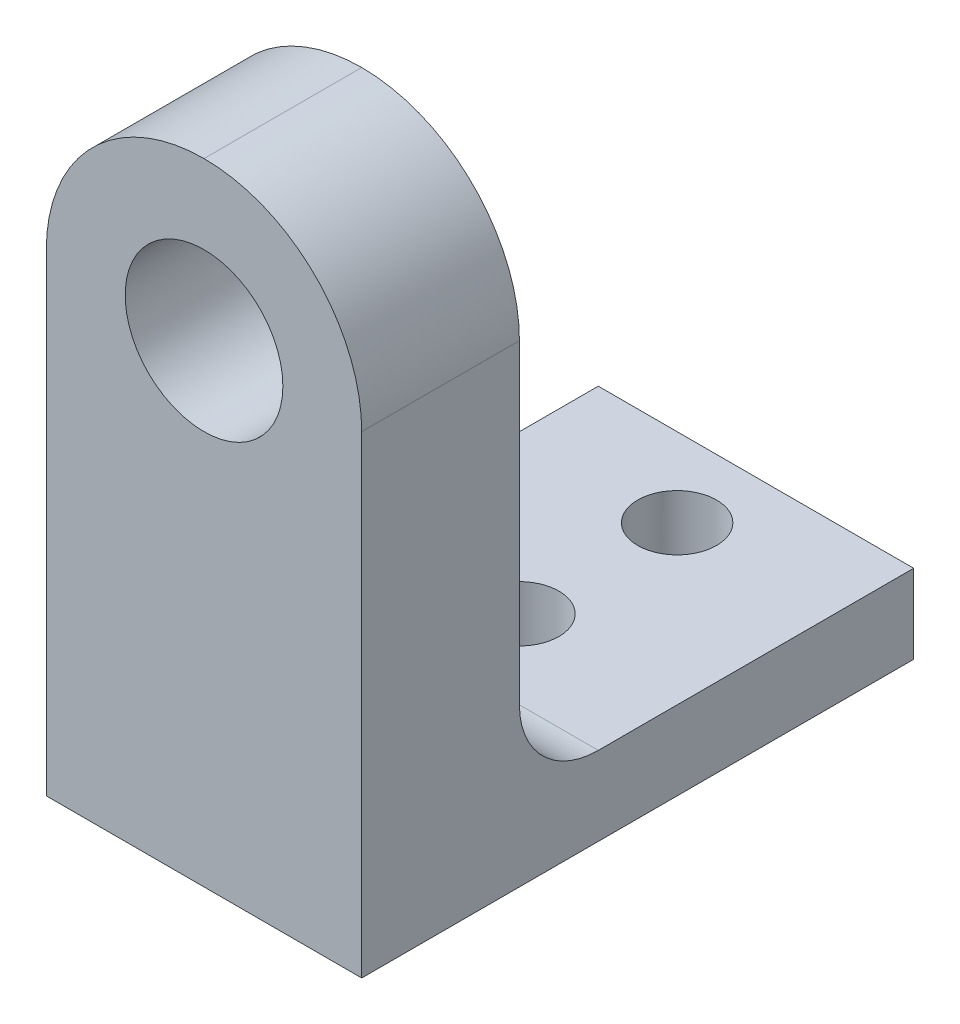
SolidWorks part; units mm, degrees
material "AISI 1015 Steel, Cold Drawn (SS)"
ref_plane "Front Plane" through (0, 0, 0) normal (0, 0, 1) x (1, 0, 0)
ref_plane "Top Plane" through (0, 0, 0) normal (0, 1, 0) x (1, 0, 0)
ref_plane "Right Plane" through (0, 0, 0) normal (1, 0, 0) x (0, 0, -1)
sketch "Sketch1" plane through (0, 0, 0) normal (1, 0, 0) x (0, 0, -1)
  line L1 (0, 0) -> (-12.7, 0)
  line L2 (0, 12.7) -> (0, 50.8)
  line L3 (0, 50.8) -> (-12.7, 50.8)
  line L4 (-12.7, 0) -> (-12.7, 50.8)
  line L5 (0, 0) -> (31.75, 0)
  line L6 (0, 0) -> (0, 6.35)
  line L7 (6.35, 6.35) -> (31.75, 6.35)
  line L8 (31.75, 0) -> (31.75, 6.35)
  arc A0 (0, 12.7) -> (6.35, 6.35) centre (6.35, 12.7) ccw
  dimension "D2" = 6.35
  dimension "D1" = 50.8
  dimension "D3" = 44.45
  dimension "D4" = 6.35
extrude "Boss-Extrude1" add sketch "Sketch1" along normal blind 25.4 contours A0 L2 L3 L4 L1 L5 L8 L7 region at (0, 19.9835, 1.0333)
fillet "Fillet1" radius 12.7 2 edges at (25.4, 50.8, 6.35) (0, 50.8, 6.35)
sketch "Sketch2" plane through (0, 0, 12.7) normal (0, 0, 1) x (1, 0, 0)
  circle A0 centre (12.7, 38.1) radius 6.35
  dimension "D1" = 12.7
extrude "Cut-Extrude1" cut sketch "Sketch2" against normal blind 25.4
sketch "Sketch3" plane through (0, 6.35, 0) normal (0, 1, 0) x (1, 0, 0)
  line L4 (25.4, 31.75) -> (0, 31.75) construction
  line L5 (12.7, 31.75) -> (12.7, 19.05) construction
  line L6 (12.7, 19.05) -> (12.7, 6.35) construction
  line L7 (25.4, 6.35) -> (0, 6.35) construction
  circle A0 centre (12.7, 25.4) radius 3.175
  circle A1 centre (12.7, 12.7) radius 3.175
  dimension "D1" = 6.35
  dimension "D2" = 6.35
extrude "Cut-Extrude2" cut sketch "Sketch3" against normal blind 25.4
